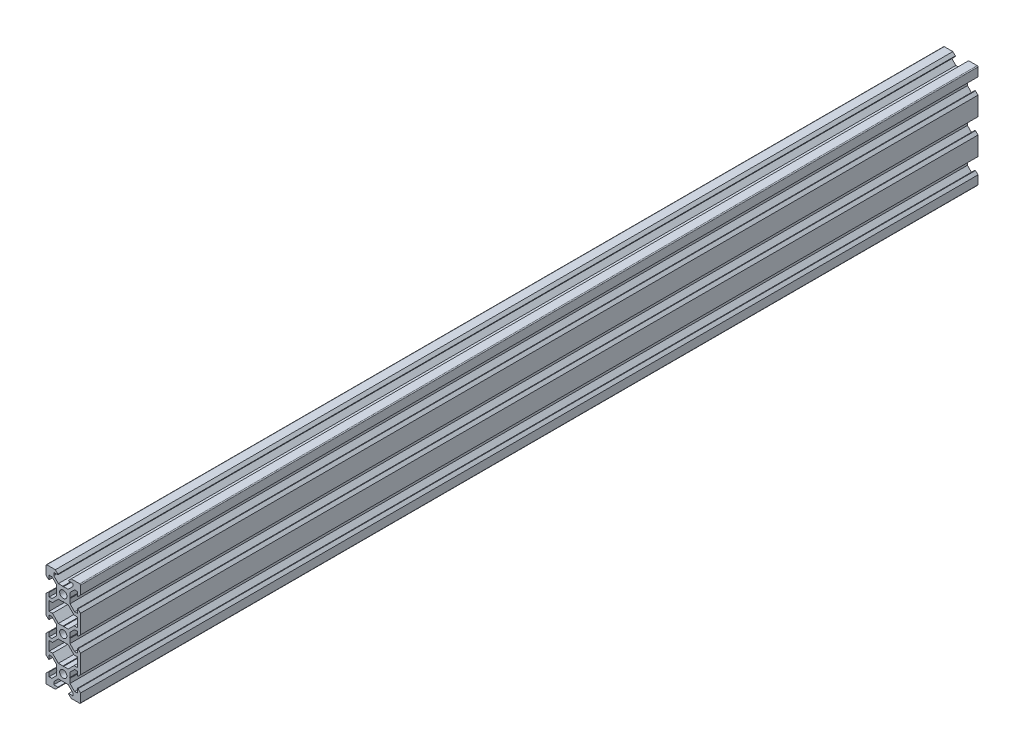
SolidWorks part; units mm, degrees
ref_plane "Plan de face" through (0, 0, 0) normal (0, 0, 1) x (1, 0, 0)
ref_plane "Plan de dessus" through (0, 0, 0) normal (0, 1, 0) x (1, 0, 0)
ref_plane "Plan de droite" through (0, 0, 0) normal (1, 0, 0) x (0, 0, -1)
ref_axis "Axe" through (0, 0, -13.782) along (0, 0, 1)
sketch "Esquisse1" plane through (0, 0, 0) normal (0, 0, 1) x (1, 0, 0)
  line L0 (0, 27.6392) -> (0, -27.6392) construction
  line L1 (-33.6074, 0) -> (33.6074, 0) construction
  line L2 (0, 0) -> (-22.2114, 22.2114) construction
  line L3 (-9.5, 10) -> (-4.58, 10)
  line L4 (-4.58, 10) -> (-3.125, 8.545)
  line L5 (-3.125, 8.545) -> (-3.125, 8.2)
  line L6 (-3.125, 8.2) -> (-5.5, 8.2)
  line L7 (-2.8393, 3.9) -> (-5.5, 6.5607)
  line L8 (-2.8393, 3.9) -> (-0.21, 3.9)
  line L9 (-5.5, 6.5607) -> (-5.5, 8.2)
  line L10 (0, 3.69) -> (0, 2.1)
  line L11 (-3.9, 2.8393) -> (-6.5607, 5.5)
  line L12 (-8.545, 3.125) -> (-8.2, 3.125)
  line L13 (-8.2, 3.125) -> (-8.2, 5.5)
  line L14 (-6.5607, 5.5) -> (-8.2, 5.5)
  line L15 (-10, 4.58) -> (-8.545, 3.125)
  line L16 (-10, 9.5) -> (-10, 4.58)
  line L17 (-0.21, 3.9) -> (0, 3.69)
  line L18 (-3.9, 2.8393) -> (-3.9, 0.21)
  line L19 (-6.2393, -12.7) -> (-8.2, -12.7)
  line L20 (-3.9, 0.21) -> (-3.69, 0)
  line L21 (-0.21, -3.9) -> (0, -3.69)
  line L22 (0, -3.69) -> (0, -2.1)
  line L23 (-6.5607, -5.5) -> (-8.2, -5.5)
  line L24 (-2.8393, -3.9) -> (-0.21, -3.9)
  line L25 (-8.545, -3.125) -> (-8.2, -3.125)
  line L26 (-10, -4.58) -> (-8.545, -3.125)
  line L27 (-8.2, -3.125) -> (-8.2, -5.5)
  line L28 (-2.8393, -3.9) -> (-6.2393, -7.3)
  line L29 (-3.9, -2.8393) -> (-6.5607, -5.5)
  line L30 (-3.9, -2.8393) -> (-3.9, -0.21)
  line L31 (-3.9, -0.21) -> (-3.69, 0)
  line L32 (-6.2393, -7.3) -> (-8.2, -7.3)
  line L33 (-8.2, -7.3) -> (-8.2, -12.7)
  line L34 (-8.2, -10) -> (-10, -10) construction
  line L35 (-10, -15.42) -> (-10, -4.58)
  line L36 (-3.9, -19.79) -> (-3.69, -20)
  line L37 (-3.9, -17.1607) -> (-3.9, -19.79)
  line L38 (-3.9, -17.1607) -> (-6.5607, -14.5)
  line L39 (-2.8393, -16.1) -> (-6.2393, -12.7)
  line L40 (-8.2, -16.875) -> (-8.2, -14.5)
  line L41 (-10, -15.42) -> (-8.545, -16.875)
  line L42 (-8.545, -16.875) -> (-8.2, -16.875)
  line L43 (-2.8393, -16.1) -> (-0.21, -16.1)
  line L44 (-6.5607, -14.5) -> (-8.2, -14.5)
  line L45 (0, -16.31) -> (0, -17.9)
  line L46 (-0.21, -16.1) -> (0, -16.31)
  line L47 (-8.2, -30) -> (-10, -30) construction
  line L48 (-3.69, -20) -> (0, -20) construction
  line L49 (-0.21, -23.9) -> (0, -23.69)
  line L50 (0, -23.69) -> (0, -22.1)
  line L51 (-6.5607, -25.5) -> (-8.2, -25.5)
  line L52 (-2.8393, -23.9) -> (-0.21, -23.9)
  line L53 (-8.545, -23.125) -> (-8.2, -23.125)
  line L54 (-10, -24.58) -> (-8.545, -23.125)
  line L55 (-8.2, -23.125) -> (-8.2, -25.5)
  line L56 (-2.8393, -23.9) -> (-6.2393, -27.3)
  line L57 (-3.9, -22.8393) -> (-6.5607, -25.5)
  line L58 (-3.9, -22.8393) -> (-3.9, -20.21)
  line L59 (-3.9, -20.21) -> (-3.69, -20)
  line L60 (-10, -24.58) -> (-10, -35.42)
  line L61 (-8.2, -32.7) -> (-8.2, -27.3)
  line L62 (-6.2393, -32.7) -> (-8.2, -32.7)
  line L63 (-3.9, -39.79) -> (-3.69, -40)
  line L64 (-3.9, -37.1607) -> (-3.9, -39.79)
  line L65 (-3.9, -37.1607) -> (-6.5607, -34.5)
  line L66 (-2.8393, -36.1) -> (-6.2393, -32.7)
  line L67 (-8.2, -36.875) -> (-8.2, -34.5)
  line L68 (-10, -35.42) -> (-8.545, -36.875)
  line L69 (-8.545, -36.875) -> (-8.2, -36.875)
  line L70 (-2.8393, -36.1) -> (-0.21, -36.1)
  line L71 (-6.5607, -34.5) -> (-8.2, -34.5)
  line L72 (0, -36.31) -> (0, -37.9)
  line L73 (-0.21, -36.1) -> (0, -36.31)
  line L74 (-3.9, -40.21) -> (-3.69, -40)
  line L75 (-6.2393, -27.3) -> (-8.2, -27.3)
  line L76 (-3.9, -42.8393) -> (-3.9, -40.21)
  line L77 (-0.21, -43.9) -> (0, -43.69)
  line L78 (-10, -49.5) -> (-10, -44.58)
  line L79 (-10, -44.58) -> (-8.545, -43.125)
  line L80 (-6.5607, -45.5) -> (-8.2, -45.5)
  line L81 (-8.2, -43.125) -> (-8.2, -45.5)
  line L82 (-8.545, -43.125) -> (-8.2, -43.125)
  line L83 (-3.9, -42.8393) -> (-6.5607, -45.5)
  line L84 (0, -43.69) -> (0, -42.1)
  line L85 (-5.5, -46.5607) -> (-5.5, -48.2)
  line L86 (-2.8393, -43.9) -> (-0.21, -43.9)
  line L87 (-2.8393, -43.9) -> (-5.5, -46.5607)
  line L88 (-3.125, -48.2) -> (-5.5, -48.2)
  line L89 (-3.125, -48.545) -> (-3.125, -48.2)
  line L90 (-4.58, -50) -> (-3.125, -48.545)
  line L91 (-9.5, -50) -> (-4.58, -50)
  arc A0 (0, -2.1) -> (0, 2.1) centre (0, 0) cw
  arc A1 (-9.5, 10) -> (-10, 9.5) centre (-9.5, 9.5) ccw
  arc A2 (0, -37.9) -> (0, -42.1) centre (0, -40) ccw
  arc A3 (-9.5, -50) -> (-10, -49.5) centre (-9.5, -49.5) cw
  arc A4 (0, -17.9) -> (0, -22.1) centre (0, -20) ccw
  point P4 (0, 0)
  point P7 (0, 0)
  point P30 (-10, 10)
  point P60 (0, -20)
  point P111 (-10, -50)
  dimension "D5" = 11
  dimension "D2" = 2.1
  dimension "D3" = 6.25
  dimension "D10" = 0.5
  dimension "D4" = 9.16
  dimension "D6" = 1.5
  dimension "D7" = 1.8
  dimension "D8" = 4.3
  dimension "D9" = 20
  dimension "D11" = 0.42
  dimension "D12" = 10
  dimension "D13" = 1.8
extrude "Boss.-Extru.1" add sketch "Esquisse1" along normal blind 520
sketch "Esquisse3" plane through (0, 0, 520) normal (0, 0, 1) x (1, 0, 0)
  line L0 (0, 0) -> (-9.8536, 9.8536) construction
  line L1 (-8.2, 8.2) -> (-8.2, 6.57)
  line L2 (-8.2, 6.57) -> (-7.54, 6.57)
  line L3 (-7.54, 6.57) -> (-6.57, 7.54)
  line L4 (-8.2, 3.125) -> (-8.2, 5.5) construction
  line L5 (-6.57, 8.2) -> (-6.57, 7.54)
  line L6 (-8.2, 8.2) -> (-6.57, 8.2)
  line L7 (-5.5, 6.5607) -> (-5.5, 8.2) construction
  line L8 (-3.69, -20) -> (0, -20) construction
  line L9 (-8.2, -48.2) -> (-6.57, -48.2)
  line L10 (-6.57, -48.2) -> (-6.57, -47.54)
  line L11 (-7.54, -46.57) -> (-6.57, -47.54)
  line L12 (-8.2, -46.57) -> (-7.54, -46.57)
  line L13 (-8.2, -48.2) -> (-8.2, -46.57)
  arc A0 (-9.5, 10) -> (-10, 9.5) centre (-9.5, 9.5) ccw construction
  point P13 (-7.055, 7.055)
  point P14 (-6.57, 7.87)
  point P26 (-7.055, -47.055)
  dimension "D1" = 1.07
extrude "Enlèv. mat.-Extru.1" [suppressed] cut sketch "Esquisse3" against normal through all
mirror "Symétrie1" about plane through (0, 3.69, 520) normal (-1, 0, 0) of "Enlèv. mat.-Extru.1", "Boss.-Extru.1"
